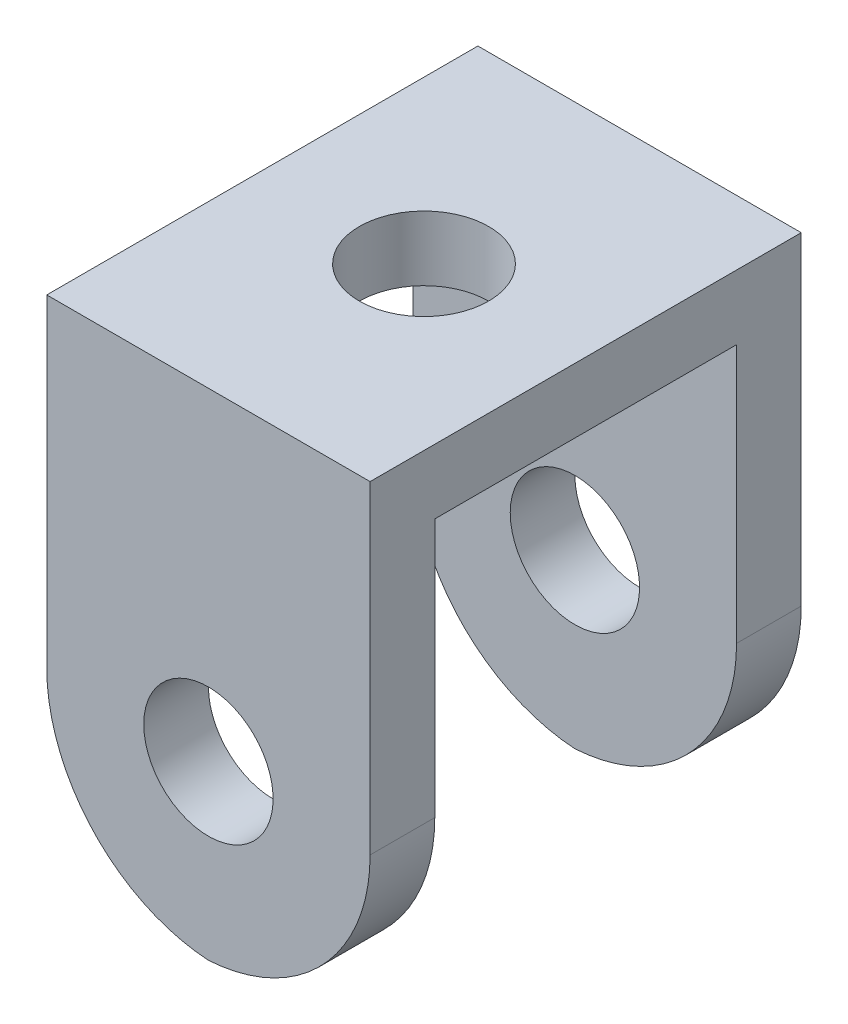
SolidWorks part; units mm, degrees
ref_plane "Front Plane" through (0, 0, 0) normal (0, 0, 1) x (1, 0, 0)
ref_plane "Top Plane" through (0, 0, 0) normal (0, 1, 0) x (1, 0, 0)
ref_plane "Right Plane" through (0, 0, 0) normal (1, 0, 0) x (0, 0, -1)
ref_axis "X-Axis" through (88.99, 0, 0) along (-1, 0, 0)
ref_axis "Y-Axis" through (0, 0, -88.99) along (0, 0, 1)
ref_axis "Z-Axis" through (0, -55, 0) along (0, 1, 0)
sketch "Sketch1" plane through (0, 0, 0) normal (0, 1, 0) x (1, 0, 0)
  line L0 (0, 88.99) -> (0, -88.99) construction
  line L1 (-7.5, 10) -> (7.5, 10)
  line L2 (-7.5, 10) -> (-7.5, -10)
  line L3 (-7.5, -10) -> (7.5, -10)
  line L4 (7.5, 10) -> (7.5, -10)
  line L5 (88.99, 0) -> (-88.99, 0) construction
  point P4 (0, 10)
  point P7 (-7.5, 0)
  dimension "D1" = 15
  dimension "D2" = 20
extrude "Boss-Extrude1" add sketch "Sketch1" along normal blind 3
sketch "Sketch2" plane through (0, 3, 0) normal (0, 1, 0) x (1, 0, 0)
  circle A0 centre (0, 0) radius 3
  dimension "D1" = 6
sketch "Sketch3" plane through (0, 0, 0) normal (0, -1, 0) x (1, 0, 0)
  line L0 (-7.5, -10) -> (-7.5, 10) construction
  line L5 (7.5, -10) -> (-7.5, -10)
  line L6 (7.5, -10) -> (7.5, -7)
  line L7 (7.5, -7) -> (-7.5, -7)
  line L8 (-7.5, -10) -> (-7.5, -7)
  line L10 (7.5, 10) -> (-7.5, 10)
  line L11 (7.5, 10) -> (7.5, 7)
  line L12 (7.5, 7) -> (-7.5, 7)
  line L13 (-7.5, 10) -> (-7.5, 7)
  point P0 (0, 0)
  dimension "D1" = 3
  dimension "D2" = 3
extrude "Boss-Extrude3" add sketch "Sketch3" along normal blind 20
sketch "Sketch4" plane through (0, 0, -10) normal (0, 0, -1) x (-1, 0, 0)
  line L0 (0, -55) -> (0, 55) construction
  line L1 (7.5, -20) -> (-7.5, -20) construction
  circle A0 centre (0, -12) radius 3
  point P2 (0, 0)
  dimension "D1" = 6
  dimension "D2" = 8
extrude "Cut-Extrude1" cut sketch "Sketch4" against normal through all
extrude "Cut-Extrude2" cut sketch "Sketch2" against normal blind 15
fillet "Fillet1" radius 8 4 edges at (-7.5, -20, 8.5) (7.5, -20, 8.5) (7.5, -20, -8.5) (-7.5, -20, -8.5)
